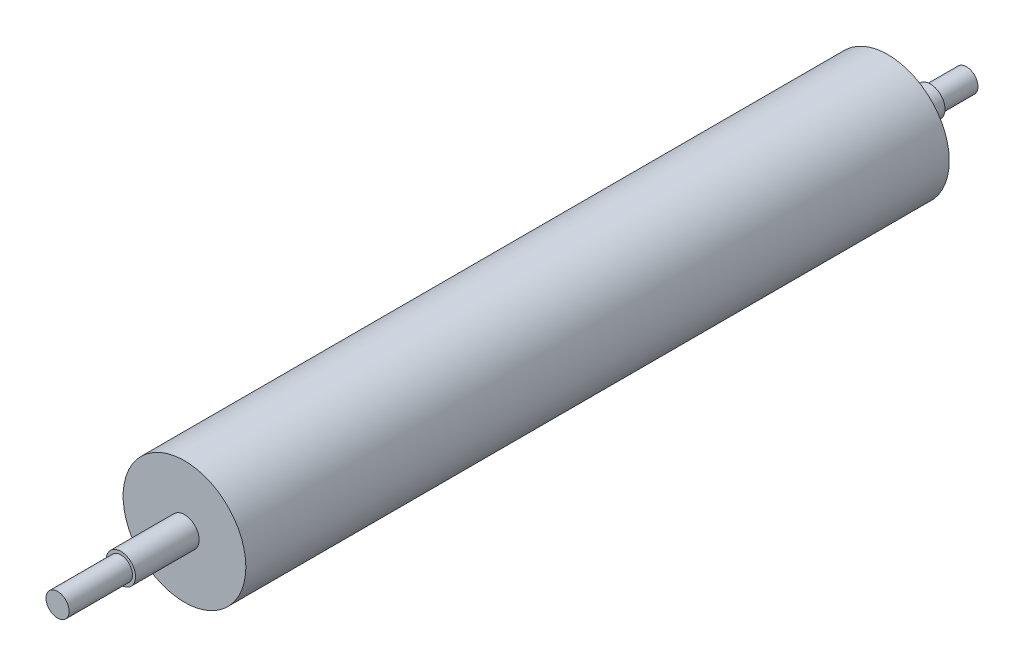
SolidWorks part; units mm, degrees
material "1060 Alloy"
ref_plane "Front Plane" through (0, 0, 0) normal (0, 0, 1) x (1, 0, 0)
ref_plane "Top Plane" through (0, 0, 0) normal (0, 1, 0) x (1, 0, 0)
ref_plane "Right Plane" through (0, 0, 0) normal (1, 0, 0) x (0, 0, -1)
sketch "Sketch1" plane through (0, 0, 0) normal (0, 0, 1) x (1, 0, 0)
  circle A0 centre (0, 0) radius 5
  circle A1 centre (0, 0) radius 3.95
  circle A2 centre (0, 0) radius 20.94
  dimension "D1" = 10
  dimension "D2" = 7.9
  dimension "D3" = 41.88
extrude "Boss-Extrude1" add sketch "Sketch1" along normal blind 240 contours A2 A0 | A0 A1 | A1 region at (-4.8586, 0, 0) region at (0, 0, 0) region at (-20.3477, 0, 0)
extrude "Boss-Extrude2" add sketch "Sketch1<3>" against normal blind 14.5 contours A0
sketch "Sketch1<3>" plane through (0, 0, 0) normal (0, 0, 1) x (1, 0, 0) same geometry as "Sketch1"
extrude "Boss-Extrude3" add sketch "Sketch1<4>" against normal blind 12.3 from surface contours A1 region at (0, 0, 0) starting at face at (5, 0, -14.5)
sketch "Sketch1<4>" plane through (0, 0, 0) normal (0, 0, 1) x (1, 0, 0) same geometry as "Sketch1"
extrude "Boss-Extrude4" add sketch "Sketch1<5>" along normal blind 21.7 from surface contours A1 | A0 A1 region at (-4.8586, 0, 0) region at (0, 0, 0) starting at face at (20.94, 0, 240)
sketch "Sketch1<5>" plane through (0, 0, 0) normal (0, 0, 1) x (1, 0, 0) same geometry as "Sketch1"
extrude "Boss-Extrude5" add sketch "Sketch1<6>" along normal blind 21.6 from surface contours A1 region at (0, 0, 0) starting at face at (5, 0, 261.7)
sketch "Sketch1<6>" plane through (0, 0, 0) normal (0, 0, 1) x (1, 0, 0) same geometry as "Sketch1"
